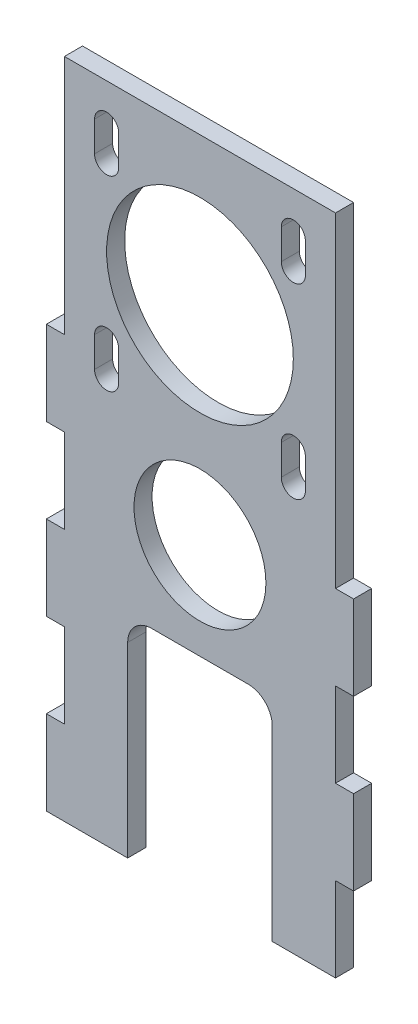
SolidWorks part; units mm, degrees
ref_plane "Front Plane" through (0, 0, 0) normal (0, 0, 1) x (1, 0, 0)
ref_plane "Top Plane" through (0, 0, 0) normal (0, 1, 0) x (1, 0, 0)
ref_plane "Right Plane" through (0, 0, 0) normal (1, 0, 0) x (0, 0, -1)
sketch "Sketch1" plane through (0, 0, 0) normal (0, 0, 1) x (1, 0, 0)
  line L1 (-22.5, -55) -> (22.5, -55)
  line L2 (-22.5, -55) -> (-22.5, 55)
  line L3 (-22.5, 55) -> (22.5, 55)
  line L4 (22.5, -55) -> (22.5, 55)
  line L5 (-22.5, -55) -> (22.5, 55) construction
  line L6 (-22.5, 55) -> (22.5, -55) construction
  point P0 (0, 0)
  dimension "D1" = 110
  dimension "D2" = 45
extrude "Boss-Extrude1" add sketch "Sketch1" along normal blind 3
sketch "Sketch2" plane through (0, 0, 3) normal (0, 0, 1) x (1, 0, 0)
  line L0 (-22.5, -55) -> (22.5, -55) construction
  line L1 (-12, -20) -> (12, -20)
  line L2 (-12, -20) -> (-12, -55)
  line L3 (-12, -55) -> (12, -55)
  line L4 (12, -20) -> (12, -55)
  line L5 (-12, -20) -> (12, -55) construction
  line L6 (-12, -55) -> (12, -20) construction
  line L7 (-22.5, 55) -> (-22.5, -55) construction
  line L8 (-22.5, 15) -> (22.5, 15) construction
  line L9 (-22.5, 15) -> (-22.5, -55) construction
  line L10 (-22.5, -55) -> (22.5, -55) construction
  line L11 (22.5, 15) -> (22.5, -55) construction
  line L12 (-22.5, 15) -> (22.5, -55) construction
  line L13 (-22.5, -55) -> (22.5, 15) construction
  line L14 (-15.5, 43.5) -> (-15.5, 48.5) construction
  line L15 (-15.5, 15) -> (15.5, 15) construction
  line L16 (-15.5, 15) -> (-15.5, 46) construction
  line L17 (-15.5, 46) -> (15.5, 46) construction
  line L18 (15.5, 15) -> (15.5, 46) construction
  line L19 (-15.5, 15) -> (15.5, 46) construction
  line L20 (-15.5, 46) -> (15.5, 15) construction
  line L21 (-17.5, 43.5) -> (-17.5, 48.5)
  line L22 (-13.5, 43.5) -> (-13.5, 48.5)
  line L23 (-15.5, 17.5) -> (-15.5, 12.5) construction
  line L24 (-13.5, 17.5) -> (-13.5, 12.5)
  line L25 (-17.5, 17.5) -> (-17.5, 12.5)
  line L26 (15.5, 17.5) -> (15.5, 12.5) construction
  line L27 (17.5, 17.5) -> (17.5, 12.5)
  line L28 (13.5, 17.5) -> (13.5, 12.5)
  line L29 (15.5, 43.5) -> (15.5, 48.5) construction
  line L30 (13.5, 43.5) -> (13.5, 48.5)
  line L31 (17.5, 43.5) -> (17.5, 48.5)
  circle A0 centre (0, -4) radius 10.95
  arc A1 (-17.5, 43.5) -> (-13.5, 43.5) centre (-15.5, 43.5) ccw
  arc A2 (-13.5, 48.5) -> (-17.5, 48.5) centre (-15.5, 48.5) ccw
  arc A3 (-13.5, 17.5) -> (-17.5, 17.5) centre (-15.5, 17.5) ccw
  arc A4 (-17.5, 12.5) -> (-13.5, 12.5) centre (-15.5, 12.5) ccw
  circle A5 centre (0, 30.5) radius 15.5
  arc A6 (17.5, 17.5) -> (13.5, 17.5) centre (15.5, 17.5) ccw
  arc A7 (13.5, 12.5) -> (17.5, 12.5) centre (15.5, 12.5) ccw
  arc A8 (13.5, 43.5) -> (17.5, 43.5) centre (15.5, 43.5) ccw
  arc A9 (17.5, 48.5) -> (13.5, 48.5) centre (15.5, 48.5) ccw
  point P0 (0, -37.5)
  point P7 (0, -20)
  point P17 (0, 30.5)
  point P24 (-15.5, 46)
  point P33 (-15.5, 15)
  point P38 (15.5, 15)
  point P43 (15.5, 46)
  dimension "D4" = 21.9
  dimension "D7" = 2
  dimension "D1" = 35
  dimension "D2" = 70
  dimension "D3" = 24
  dimension "D5" = 16
  dimension "D6" = 31
  dimension "D8" = 5
extrude "Cut-Extrude1" cut sketch "Sketch2" against normal through all
fillet "Fillet1" radius 4 2 edges at (12, -20, 1.5) (-12, -20, 1.5)
sketch "Sketch3" plane through (0, 0, 3) normal (0, 0, 1) x (1, 0, 0)
  line L0 (22.5, -55) -> (22.5, 55) construction
  line L1 (-22.5, -55) -> (22.5, -55) construction
  line L2 (-22.5, -55) -> (-22.5, 15) construction
  line L3 (-22.5, 15) -> (22.5, 15) construction
  line L4 (22.5, -55) -> (22.5, 15) construction
  line L5 (-22.5, -13) -> (-22.5, -27)
  line L6 (-22.5, 15) -> (-25.5, 15)
  line L7 (-22.5, 15) -> (-22.5, 1)
  line L8 (-22.5, 1) -> (-25.5, 1)
  line L9 (-25.5, 15) -> (-25.5, 1)
  line L10 (-22.5, -27) -> (-25.5, -27)
  line L11 (-25.5, -13) -> (-25.5, -27)
  line L12 (-22.5, -13) -> (-25.5, -13)
  line L13 (-22.5, -41) -> (-22.5, -55)
  line L14 (-22.5, -55) -> (-25.5, -55)
  line L15 (-25.5, -41) -> (-25.5, -55)
  line L16 (-22.5, -41) -> (-25.5, -41)
  line L18 (-22.5, 55) -> (-22.5, -55) construction
  line L20 (22.5, 1) -> (25.5, 1)
  line L21 (22.5, 1) -> (22.5, -13)
  line L22 (22.5, -13) -> (25.5, -13)
  line L23 (25.5, 1) -> (25.5, -13)
  line L24 (22.5, -27) -> (25.5, -27)
  line L25 (22.5, -27) -> (22.5, -41)
  line L26 (22.5, -41) -> (25.5, -41)
  line L27 (25.5, -27) -> (25.5, -41)
  dimension "D1" = 70
  dimension "D2" = 3
  dimension "D3" = 14
  dimension "D4" = 3
extrude "Boss-Extrude2" add sketch "Sketch3" against normal up to surface (3 mm away) up to face at (15.5, 46, 0)
equation "\"pulley_pitch_diam\"= 12.73mm"
equation "\"pulley_total_width\"= 16mm"
equation "\"pulley_total_diam\"= 16mm"
equation "\"belt_width\"= 6mm"
equation "\"material_thickness\"= 3mm"
equation "\"shaft_diam\"= 8mm"
equation "\"bearing_od\"= 22mm"
equation "\"bearing_thickness\"= 7mm"
equation "\"D1@Boss-Extrude1\"=\"material_thickness\""
equation "\"D3@Sketch2\"=\"pulley_total_width\" * 1.5"
equation "\"D4@Sketch2\"=\"bearing_od\" - 0.1"
equation "\"D2@Sketch3\"=\"material_thickness\""
equation "\"D5@Sketch2\"=\"pulley_total_diam\""
